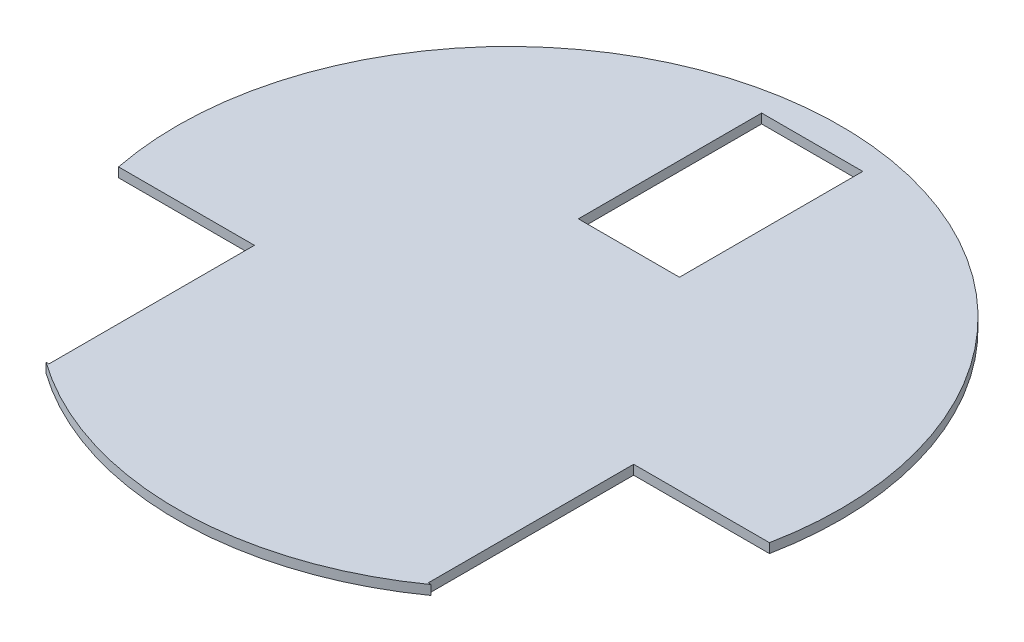
SolidWorks part; units mm, degrees
ref_plane "前视基准面" through (0, 0, 0) normal (0, 0, 1) x (1, 0, 0)
ref_plane "上视基准面" through (0, 0, 0) normal (0, 1, 0) x (1, 0, 0)
ref_plane "右视基准面" through (0, 0, 0) normal (1, 0, 0) x (0, 0, -1)
sketch "草图1" plane through (0, 0, 0) normal (0, 1, 0) x (1, 0, 0)
  circle A0 centre (0, 0) radius 105
  dimension "D1" = 210
extrude "原型底盘" add sketch "草图1" along normal blind 3
sketch "草图5" plane through (0, 3, 0) normal (0, 1, 0) x (1, 0, 0)
  line L0 (0, 0) -> (0, -20)
  line L1 (-105, -20.5) -> (-60, -20.5)
  line L2 (-105, -20.5) -> (-105, -85.5)
  line L3 (-105, -85.5) -> (-60, -85.5)
  line L4 (-60, -20.5) -> (-60, -85.5)
  line L5 (60, -20.5) -> (60, -85.5)
  line L6 (105, -85.5) -> (60, -85.5)
  line L7 (105, -20.5) -> (105, -85.5)
  line L8 (105, -20.5) -> (60, -20.5)
  point P4 (-60, -53)
  point P12 (0, 0)
  circle M4 centre (0, 0) radius 105
  dimension "D1" = 53
  dimension "D2" = 65
  dimension "D3" = 120
  dimension "D4" = 45
extrude "后轮空位" cut sketch "草图5" against normal through all contours L4 L1 L3 M4 | L8 L5 L6 M4 region at (-76.4799, 3, 45.1745) region at (76.4799, 3, 45.1745)
sketch "草图6" plane through (0, 3, 0) normal (0, 1, 0) x (1, 0, 0)
  line L1 (-16, 96) -> (16, 96)
  line L2 (-16, 96) -> (-16, 38)
  line L3 (-16, 38) -> (16, 38)
  line L4 (16, 96) -> (16, 38)
  point P4 (0, 38)
  point P6 (16, 67)
  dimension "D1" = 0
  dimension "D2" = 32
  dimension "D3" = 58
  dimension "D4" = 67
extrude "前轮空位" cut sketch "草图6" against normal through all
